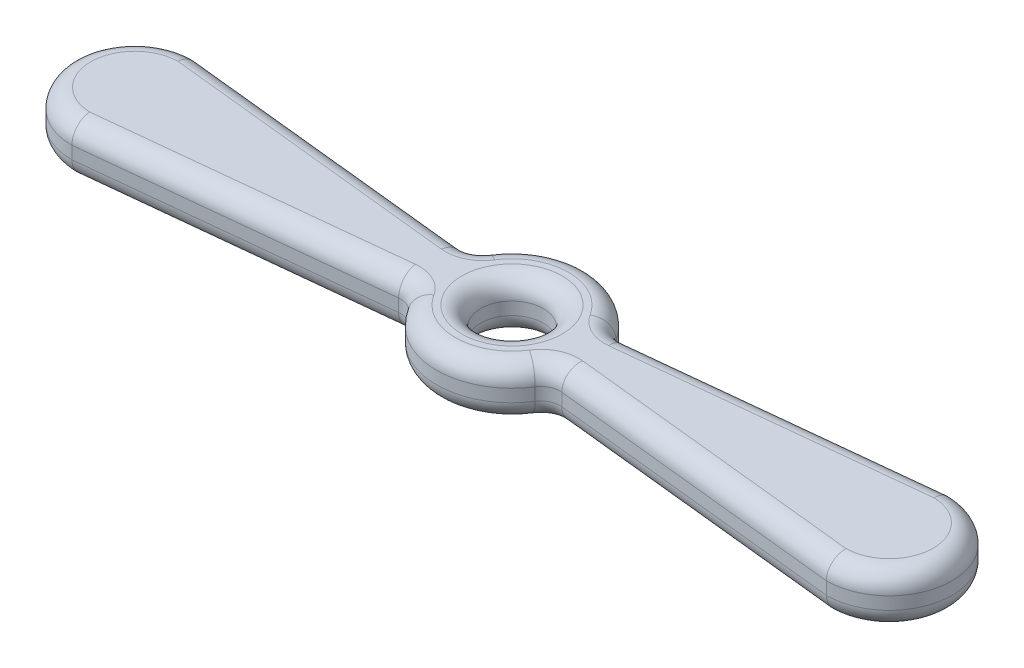
SolidWorks part; units mm, degrees
ref_plane "Front Plane" through (0, 0, 0) normal (0, 0, 1) x (1, 0, 0)
ref_plane "Top Plane" through (0, 0, 0) normal (0, 1, 0) x (1, 0, 0)
ref_plane "Right Plane" through (0, 0, 0) normal (1, 0, 0) x (0, 0, -1)
sketch "Sketch1" plane through (0, 0, 0) normal (0, 1, 0) x (1, 0, 0)
  line L1 (-60, 10) -> (-12.9761, 5.0576)
  line L2 (-60, 0) -> (-48.8939, 0) construction
  line L3 (0, 12) -> (0, 31.6542) construction
  line L4 (-60, -10) -> (-12.9761, -5.0576)
  line L5 (60, 10) -> (12.9761, 5.0576)
  line L6 (60, -10) -> (12.9761, -5.0576)
  arc A2 (-10.13, -6.4329) -> (10.13, -6.4329) centre (0, 0) ccw
  arc A3 (-57.9209, 9.7815) -> (-57.9209, -9.7815) centre (-60, 0) ccw
  arc A4 (57.9209, 9.7815) -> (57.9209, -9.7815) centre (60, 0) cw
  arc A5 (10.13, 6.4329) -> (-10.13, 6.4329) centre (0, 0) ccw
  circle A6 centre (0, 0) radius 5
  arc A7 (12.9761, 5.0576) -> (10.13, 6.4329) centre (12.6625, 8.0412) cw
  arc A8 (12.9761, -5.0576) -> (10.13, -6.4329) centre (12.6625, -8.0412) ccw
  arc A9 (-12.9761, -5.0576) -> (-10.13, -6.4329) centre (-12.6625, -8.0412) cw
  arc A10 (-12.9761, 5.0576) -> (-10.13, 6.4329) centre (-12.6625, 8.0412) ccw
  point P20 (0, 0)
  point P22 (10.9773, 4.8475)
  point P25 (10.9773, -4.8475)
  point P29 (-10.9773, -4.8475)
  point P32 (-10.9773, 4.8475)
  dimension "D1" = 24
  dimension "D3" = 60
  dimension "D2" = 20
  dimension "D5" = 3
  dimension "D4" = 6
extrude "Boss-Extrude1" add sketch "Sketch1" along normal blind 8 contours A10 L1 A3 L4 A9 A2 A8 L6 A4 L5 A7 A5 A6
fillet "Fillet2" radius 3 26 edges at (0, 8, 5) (0, 8, -12) (11.3572, 8, -5.34) (36.4881, 8, -7.5288) (70, 8, 0) (36.4881, 8, 7.5288) (11.3572, 8, 5.34) (0, 8, 12) (-11.3572, 8, 5.34) (-36.4881, 8, 7.5288) (-70, 8, 0) (-36.4881, 8, -7.5288) (-11.3572, 8, -5.34) (0, 0, 5) (-36.4881, 0, -7.5288) (-70, 0, 0) (-36.4881, 0, 7.5288) (-11.3572, 0, 5.34) (0, 0, 12) (11.3572, 0, 5.34) (36.4881, 0, 7.5288) (70, 0, 0) (36.4881, 0, -7.5288) (11.3572, 0, -5.34) (0, 0, -12) (-11.3572, 0, -5.34)
